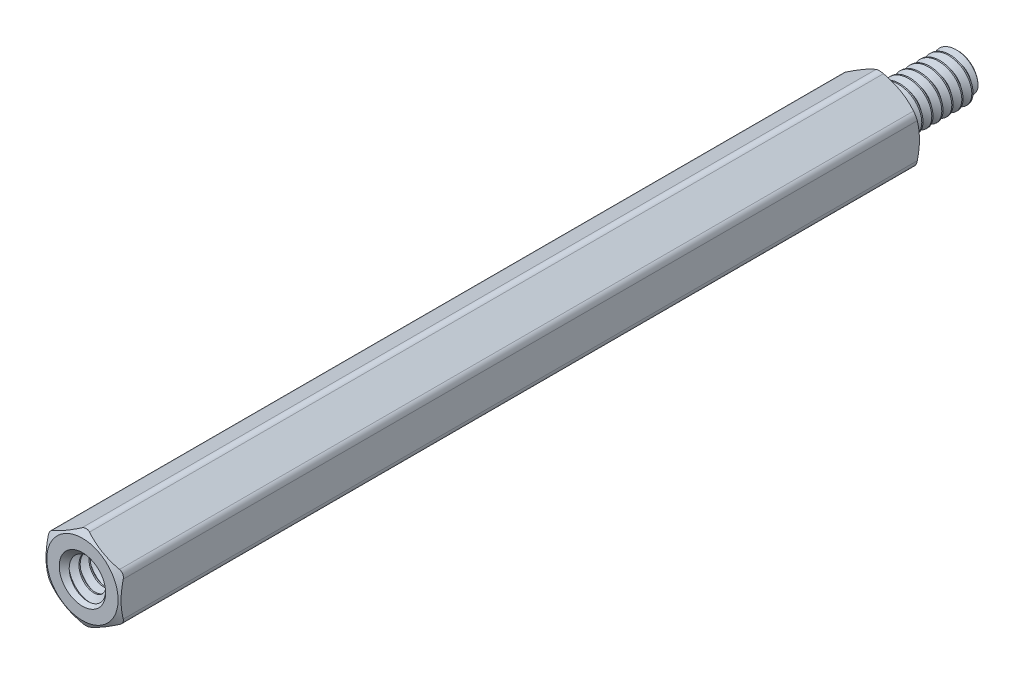
SolidWorks part; units mm, degrees
ref_plane "Front Plane" through (0, 0, 0) normal (0, 0, 1) x (1, 0, 0)
ref_plane "Top Plane" through (0, 0, 0) normal (0, 1, 0) x (1, 0, 0)
ref_plane "Right Plane" through (0, 0, 0) normal (1, 0, 0) x (0, 0, -1)
sketch "Sketch1" plane through (0, 0, 0) normal (0, 0, 1) x (1, 0, 0)
  line L1 (2.3813, 1.3748) -> (0, 2.7496)
  line L2 (0, 2.7496) -> (-2.3812, 1.3748)
  line L3 (-2.3812, 1.3748) -> (-2.3812, -1.3748)
  line L4 (-2.3812, -1.3748) -> (0, -2.7496)
  line L5 (0, -2.7496) -> (2.3813, -1.3748)
  line L6 (2.3813, -1.3748) -> (2.3813, 1.3748)
  circle A0 centre (0, 0) radius 2.3812 construction
  point P10 (0, -2.3812)
  dimension "Hex Size" = 4.7625
sketch "Sketch2" plane through (0, 0, 0) normal (1, 0, 0) x (0, 0, -1)
  line L0 (4.7625, 0) -> (-50.8, 0) construction
  line L2 (0, 1.4224) -> (0, -1.4224) construction
  line L3 (-44.45, 1.4224) -> (-44.45, -1.4224) construction
  line L4 (-51.3953, 1.4911) -> (-51.0778, 0.9412) construction
  line L5 (-51.0778, 0.9412) -> (-50.7603, 1.4911) construction
  line L6 (-50.7603, 1.4911) -> (-51.3953, 1.4911) construction
  line L7 (-51.3556, 1.4224) -> (-50.8, 1.4224) construction
  line L8 (-51.1175, 1.01) -> (-51.0381, 1.01) construction
  line L9 (-51.0778, 1.01) -> (-51.0778, 0.9412) construction
  line L10 (-51.0778, 1.4224) -> (-51.0778, 1.4911) construction
  line L11 (4.7228, 1.4911) -> (5.3578, 1.4911) construction
  line L12 (5.3578, 1.4911) -> (5.0403, 0.9412) construction
  line L13 (5.0403, 0.9412) -> (4.7228, 1.4911) construction
  line L14 (4.7625, 1.4224) -> (5.3181, 1.4224) construction
  line L15 (5.0006, 1.01) -> (5.08, 1.01) construction
  line L16 (5.0403, 1.01) -> (5.0403, 0.9412) construction
  line L17 (5.0403, 1.4224) -> (5.0403, 1.4911) construction
  line L18 (0, 2.7496) -> (-50.8, 2.7496) construction
  point P6 (0, 0)
  point P9 (-44.45, 0)
  dimension "Length" = 50.8
sketch "Sketch3" plane through (0, 0, 0) normal (1, 0, 0) x (0, 0, -1)
  line L0 (-44.45, 0) -> (4.7625, 0)
  line L1 (-44.45, 1.4224) -> (-44.45, -1.4224) construction
  line L2 (4.7625, 0) -> (4.7625, 1.2637)
  line L3 (4.7625, 1.2637) -> (4.6038, 1.4224)
  line L4 (4.6038, 1.4224) -> (0.8096, 1.4224)
  line L5 (0.8096, 1.4224) -> (0.5715, 1.01)
  line L6 (-44.45, 0) -> (-44.45, 1.2636)
  line L7 (-44.45, 1.2636) -> (-44.6088, 1.4224)
  line L8 (-44.6088, 1.4224) -> (-50.6413, 1.4224)
  line L9 (-50.6413, 1.4224) -> (-50.8, 1.5811)
  line L10 (4.6038, 0) -> (4.6038, -1.4224) construction
  line L11 (-50.8, 1.5811) -> (-50.8, 2.3812)
  line L12 (-50.8, 2.3812) -> (0, 2.3812)
  line L14 (0.5715, 1.01) -> (0.1587, 1.01)
  line L15 (0, 1.1687) -> (0, 2.3812)
  arc A0 (0, 1.1687) -> (0.1587, 1.01) centre (0.1587, 1.1687) ccw
  point P5 (-50.8, -2.3812)
  point P8 (-49.2125, -1.4224)
  point P9 (3.175, -1.4224)
  point P27 (0, 1.01)
  dimension "D4" = 0.1588
  dimension "D2" = 0.1588
  dimension "D1" = 45
  dimension "D6" = 1.5875
  dimension "D7" = 60
  dimension "D3" = 1.5875
  dimension "D5" = 0.5715
revolve "Revolve1" add sketch "Sketch3" angle 360 about L0 region at (0, 1.1996, 22.1789)
sketch "Sketch4" plane through (0, 0, 50.8) normal (0, 0, 1) x (1, 0, 0)
  line L0 (0, 2.3812) -> (0, 1.4224) construction
  line L1 (-2.3812, 1.3748) -> (-2.3812, -1.3748)
  line L2 (-2.3812, -1.3748) -> (0, -2.7496)
  line L3 (0, -2.7496) -> (2.3812, -1.3748)
  line L4 (2.3812, -1.3748) -> (2.3812, 1.3748)
  line L5 (2.3812, 1.3748) -> (0, 2.7496)
  line L6 (0, 2.7496) -> (-2.3812, 1.3748)
  circle A0 centre (0, 0) radius 2.3812 construction
  circle A1 centre (0, 0) radius 1.9018
  circle A2 centre (0, 0) radius 2.3812 construction
  point P16 (0, 1.9018)
extrude "Boss-Extrude1" add sketch "Sketch4" against normal up to surface (50.8 mm away) up to face at (0, 2.3812, 0)
sketch "Sketch5" plane through (0, 0, 50.8) normal (0, 0, 1) x (1, 0, 0)
  line L0 (-0.8159, 1.1652) -> (0.8159, -1.1652) construction
  line L1 (0, 1.4224) -> (0, -1.4224) construction
  line L3 (0, -2.9435) -> (0, 2.9435) construction
  circle A0 centre (0, 0) radius 2.2622
  point P11 (0.8159, -1.1652)
  dimension "D1" = 4.5244
  dimension "D2" = 35
extrude "Cut-Extrude1" cut sketch "Sketch5" against normal through all draft 60 flip side to cut
sketch "Sketch6" plane through (0, 0, 0) normal (0, 0, -1) x (-1, 0, 0)
  circle A0 centre (0, 0) radius 2.2622
  circle A1 centre (0, 0) radius 2.2622 construction
extrude "Cut-Extrude2" cut sketch "Sketch6" against normal through all draft 60 flip side to cut
fillet "Fillet1" radius 0.4763 6 edges at (0, 2.7496, 25.4) (-2.3812, -1.3748, 25.4) (0, -2.7496, 25.4) (2.3812, -1.3748, 25.4) (2.3812, 1.3748, 25.4) (-2.3812, 1.3748, 25.4)
sketch "Drawing1" plane through (0, 0, 0) normal (1, 0, 0) x (0, 0, -1)
  line L0 (-50.8, 1.4224) -> (-44.45, 1.4224) construction
  line L1 (-44.45, 1.4224) -> (-44.45, -1.4224) construction
  line L2 (-44.45, -1.4224) -> (-50.8, -1.4224) construction
sketch "Sketch7" plane through (0, 0, 0) normal (-1, 0, 0) x (0, 0, 1)
  line L0 (-5.0006, 1.01) -> (-5.08, 1.01)
  line L1 (-5.08, 1.01) -> (-5.338, 1.4568)
  line L2 (-5.3578, 1.4911) -> (-5.0403, 0.9412) construction
  line L3 (-5.338, 1.4568) -> (-4.7427, 1.4568)
  line L4 (-5.0403, 0.9412) -> (-4.7228, 1.4911) construction
  line L5 (-4.7427, 1.4568) -> (-5.0006, 1.01)
  line L6 (-5.0403, 1.4224) -> (-5.0403, 1.4911) construction
  point P12 (-5.0403, 1.4568)
sketch "Sketch8" plane through (0, 0, -4.7625) normal (0, 0, -1) x (-1, 0, 0)
  circle A0 centre (0, 0) radius 1.4224
curve "Helix/Spiral1" pitch 0.635 height 4.6196 radius 1.4224 centre (0, 0, -4.7625) axis (0, 0, 1) start towards (0, 1, 0)
sweep "Cut-Sweep1" cut profiles "Sketch7" path "Helix/Spiral1" align with end faces yes
sketch "Sketch9" plane through (0, 0, 44.45) normal (0, 0, 1) x (1, 0, 0)
  circle A0 centre (0, 0) radius 1.5811
extrude "Boss-Extrude2" add sketch "Sketch9" along normal up to surface (6.35 mm away) up to face at (0, 1.5811, 50.8)
sketch "Sketch10" plane through (0, 0, 0) normal (1, 0, 0) x (0, 0, -1)
  line L0 (4.7625, 0) -> (-50.8, 0) construction
  line L1 (-44.45, 1.4224) -> (-50.8, 1.4224)
  line L2 (-44.45, 1.4224) -> (-44.45, 0)
  line L3 (-44.45, 0) -> (-50.8, 0)
  line L4 (-50.8, 1.4224) -> (-50.8, 0)
revolve "Revolve2" add sketch "Sketch10" angle 360 about L0
sketch "Sketch11" plane through (0, 0, 50.8) normal (0, 0, 1) x (1, 0, 0)
  circle A0 centre (0, 0) radius 1.4224
  circle A1 centre (0, 0) radius 1.4224 construction
sketch "Sketch12" plane through (0, 0, 0) normal (1, 0, 0) x (0, 0, -1)
  line L0 (-51.1175, 1.01) -> (-51.0381, 1.01)
  line L1 (-51.0381, 1.01) -> (-50.7802, 1.4568)
  line L2 (-51.0778, 0.9412) -> (-50.7603, 1.4911) construction
  line L3 (-50.7802, 1.4568) -> (-51.3755, 1.4568)
  line L4 (-51.3953, 1.4911) -> (-51.0778, 0.9412) construction
  line L5 (-51.3755, 1.4568) -> (-51.1175, 1.01)
  line L6 (-51.0778, 1.4224) -> (-51.0778, 1.4911) construction
  point P12 (-51.0778, 1.4568)
curve "Helix/Spiral2" pitch 0.635 height 6.985 radius 1.4224 centre (0, 0, 50.8) axis (0, 0, -1) start towards (0, 1, 0)
sweep "Cut-Sweep2" cut profiles "Sketch12" path "Helix/Spiral2" align with end faces yes
combine bodies "Combine1" operation type subtract main body 113 bodies to subtract 114
sketch "Sketch13" plane through (0, 0, 50.8) normal (0, 0, 1) x (1, 0, 0)
  circle A0 centre (0, 0) radius 1.4732
  dimension "D1" = 0.0508
extrude "Cut-Extrude3" cut sketch "Sketch13" against normal through all draft 45
equation "\"Thread Pitch (B)/8@Sketch2\"=\"Thread Pitch (B)@Sketch2\"/8"
equation "\"Thread Pitch (A)/8@Sketch2\"=\"Thread Pitch (A)@Sketch2\"/8"
equation "\"D1@Sketch5\" = \"Hex Size@Sketch1\" * .95"
equation "\"D1@Fillet1\" = \"Hex Size@Sketch1\" * .1"
equation "\"D2@Sketch3\" = \"Thread Pitch (A)@Sketch2\" * .25"
equation "\"D4@Sketch3\" = \"D2@Sketch3\""
equation "\"D6@Sketch3\" = \"Thread Pitch (A)@Sketch2\" * 2.5"
equation "\"D3@Helix/Spiral1\" = \"Thread Length (A)@Sketch2\" - \"D5@Sketch3\" * .25"
equation "\"D4@Helix/Spiral1\" = \"Thread Pitch (A)@Sketch2\""
equation "\"D3@Sketch3\" = \"Thread Pitch (B)@Sketch2\" * 2.5"
equation "\"D5@Sketch3\" = \"Thread Length (A)@Sketch2\" * .12"
equation "\"D3@Helix/Spiral2\" = \"Minimum Thread Length (B)@Sketch2\" + \"Thread Pitch (B)@Sketch2\""
equation "\"D4@Helix/Spiral2\" = \"Thread Pitch (B)@Sketch2\""
